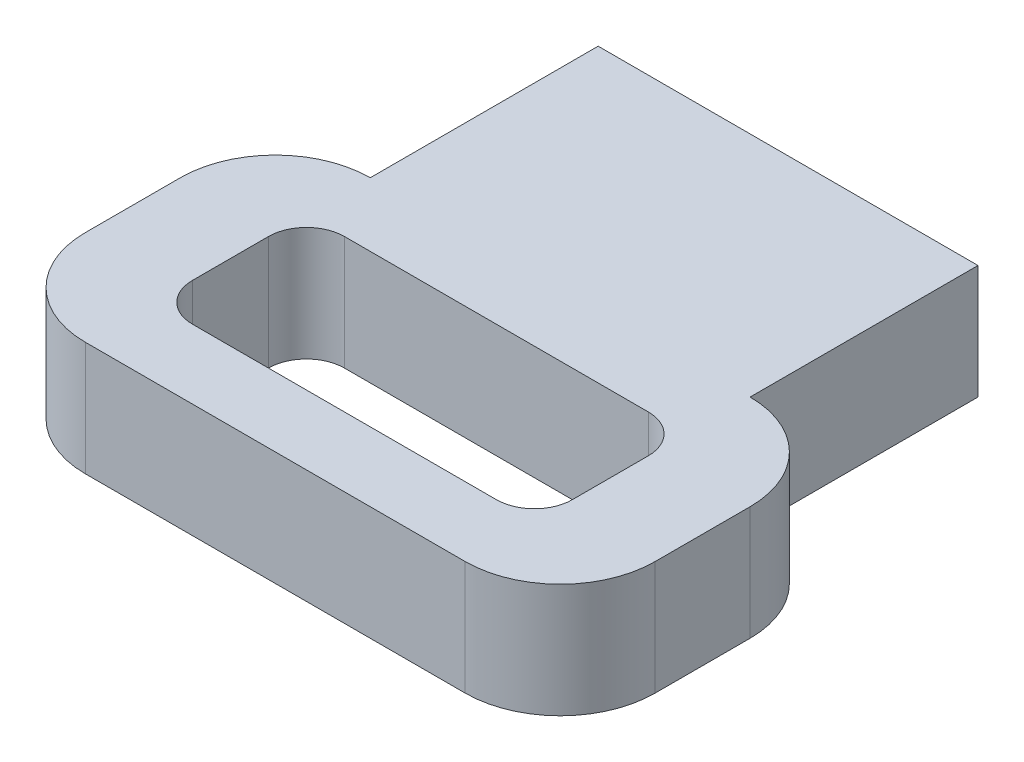
SolidWorks part; units mm, degrees
ref_plane "Front Plane" through (0, 0, 0) normal (0, 0, 1) x (1, 0, 0)
ref_plane "Top Plane" through (0, 0, 0) normal (0, 1, 0) x (1, 0, 0)
ref_plane "Right Plane" through (0, 0, 0) normal (1, 0, 0) x (0, 0, -1)
sketch "Sketch1" plane through (0, 0, 0) normal (0, 0, 1) x (1, 0, 0)
  line L1 (25.4, -7.62) -> (-25.4, -7.62)
  line L2 (25.4, -7.62) -> (25.4, 7.62)
  line L3 (25.4, 7.62) -> (-25.4, 7.62)
  line L4 (-25.4, -7.62) -> (-25.4, 7.62)
  line L5 (25.4, -7.62) -> (-25.4, 7.62) construction
  line L6 (25.4, 7.62) -> (-25.4, -7.62) construction
  point P0 (0, 0)
  dimension "D1" = 50.8
  dimension "D2" = 15.24
extrude "Boss-Extrude2" add sketch "Sketch1" along normal blind 30.48
sketch "Sketch2" plane through (0, 0, 30.48) normal (0, 0, 1) x (1, 0, 0)
  line L0 (25.4, 7.62) -> (-25.4, 7.62) construction
  line L1 (-38.1, -7.62) -> (38.1, -7.62)
  line L2 (-38.1, -7.62) -> (-38.1, 7.62)
  line L3 (-38.1, 7.62) -> (38.1, 7.62)
  line L4 (38.1, -7.62) -> (38.1, 7.62)
  line L5 (-38.1, -7.62) -> (38.1, 7.62) construction
  line L6 (-38.1, 7.62) -> (38.1, -7.62) construction
  point P0 (0, 0)
  dimension "D1" = 0
  dimension "D2" = 76.2
extrude "Boss-Extrude3" add sketch "Sketch2" along normal blind 38.1
sketch "Sketch3" plane through (0, -7.62, 0) normal (0, -1, 0) x (1, 0, 0)
  line L0 (0, 68.58) -> (0, 0) construction
  line L1 (-38.1, 68.58) -> (38.1, 68.58) construction
  line L3 (-25.4, 59.3273) -> (25.4, 59.3273)
  line L4 (-25.4, 59.3273) -> (-25.4, 39.0073)
  line L5 (-25.4, 39.0073) -> (25.4, 39.0073)
  line L6 (25.4, 59.3273) -> (25.4, 39.0073)
  line L7 (-25.4, 59.3273) -> (25.4, 39.0073) construction
  line L8 (-25.4, 39.0073) -> (25.4, 59.3273) construction
  point P5 (0, 49.1673)
  dimension "D1" = 20.32
  dimension "D2" = 50.8
extrude "Cut-Extrude1" cut sketch "Sketch3" against normal through all contours L3 L6 L5 L4
fillet "Fillet1" radius 5.08 4 edges at (25.4, 0, 39.0073) (-25.4, 0, 39.0073) (25.4, 0, 59.3273) (-25.4, 0, 59.3273)
fillet "Fillet4" radius 12.7 4 edges at (38.1, 0, 30.48) (38.1, 0, 68.58) (-38.1, 0, 30.48) (-38.1, 0, 68.58)
